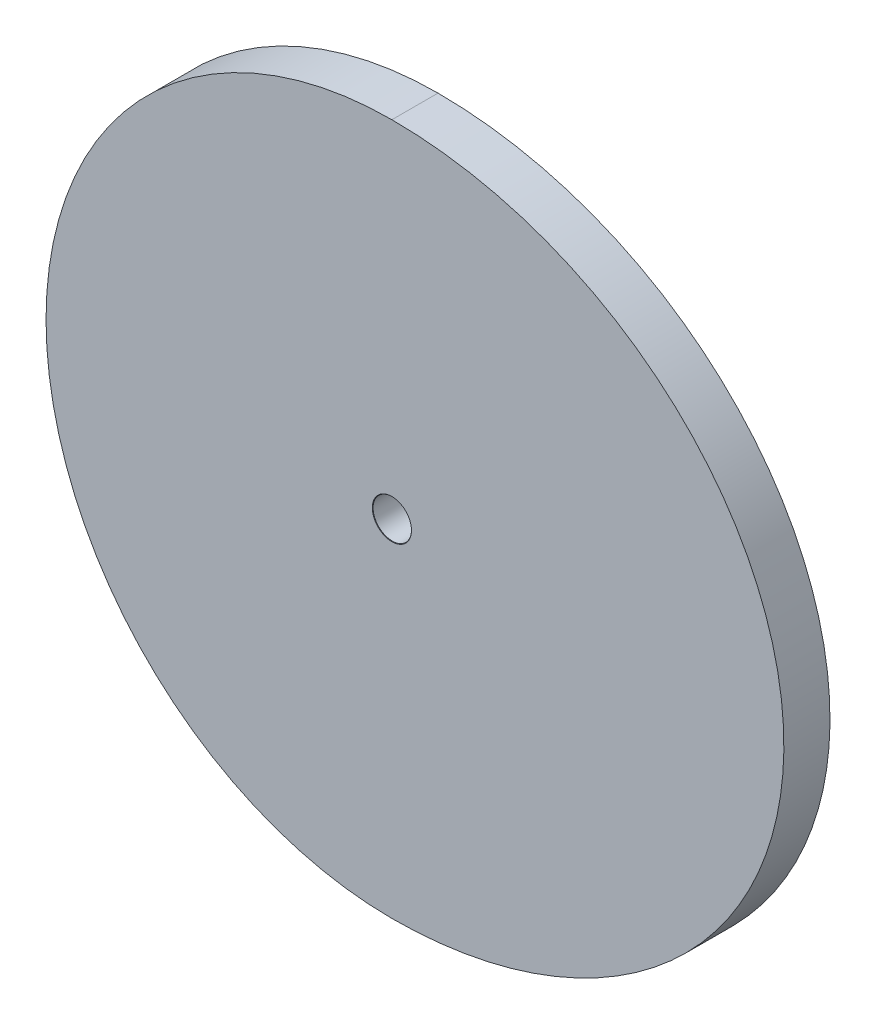
SolidWorks part; units mm, degrees
ref_plane "Front Plane" through (0, 0, 0) normal (0, 0, 1) x (1, 0, 0)
ref_plane "Top Plane" through (0, 0, 0) normal (0, 1, 0) x (1, 0, 0)
ref_plane "Right Plane" through (0, 0, 0) normal (1, 0, 0) x (0, 0, -1)
sketch "Sketch1" plane through (0, 0, 0) normal (0, 0, 1) x (1, 0, 0)
  line L1 (15.5, 0) -> (41, 0) construction
  line L2 (15.5, 22.5) -> (15.5, -22.5) construction
  arc A0 (15.5, 22.5) -> (15.5, -22.5) centre (15.5, 0) ccw
  ellipse E0 centre (15.5, 0) end of major axis (41, 0) minor radius 22.5 (15.5, -22.5) -> (15.5, 22.5) ccw
  point P3 (38, 0)
  point P9 (15.5, 0)
  dimension "D1" = 45
  dimension "D2" = 3
extrude "Boss-Extrude1" add sketch "Sketch1" along normal blind 3 contours A0 E0
hole_wizard "Ø2.5mm Dowel Hole1" positions "Sketch2" profile "Sketch3" hole size "Ø2.5" standard "ANSI Metric" end condition through all
sketch "Sketch2" plane through (0, 0, 3) normal (0, 0, 1) x (1, 0, 0)
  point P0 (15.5, 0)
sketch "Sketch3" plane through (15.5, 0, 3) normal (1, 0, 0) x (0, -1, 0)
  line L0 (0, 0) -> (0, 3)
  line L1 (0, 3) -> (1.25, 3)
  line L2 (1.25, 3) -> (1.25, 0.025)
  line L3 (1.25, 0.025) -> (1.275, 0)
  line L5 (1.275, 0) -> (0, 0)
  line L6 (-1.25, 0.025) -> (-1.275, 0) construction
  line L11 (0, -6.35) -> (0, 107.95) construction
  dimension "Thru Hole Dia." = 2.5
  dimension "Thru Hole Depth" = 3
  dimension "Near C'Sink Dia." = 2.55
  dimension "Near C'Sink Angle" = 90
